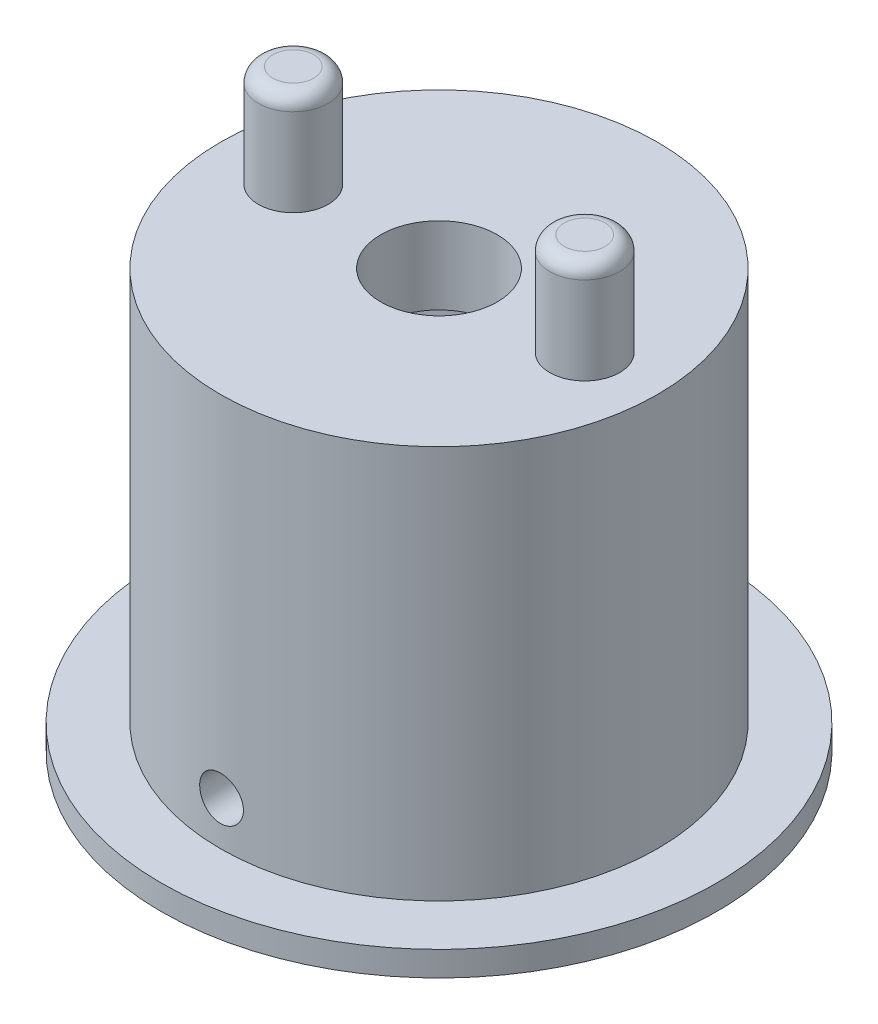
SolidWorks part; units mm, degrees
ref_plane "Front Plane" through (0, 0, 0) normal (0, 0, 1) x (1, 0, 0)
ref_plane "Top Plane" through (0, 0, 0) normal (0, 1, 0) x (1, 0, 0)
ref_plane "Right Plane" through (0, 0, 0) normal (1, 0, 0) x (0, 0, -1)
sketch "Sketch1" plane through (0, 0, 0) normal (0, 1, 0) x (1, 0, 0)
  circle A0 centre (0, 0) radius 15
  dimension "D1" = 30
extrude "Boss-Extrude1" add sketch "Sketch1" along normal blind 27
sketch "Sketch2" plane through (0, 0, 0) normal (0, -1, 0) x (1, 0, 0)
  circle A0 centre (0, 0) radius 19.07
  dimension "D1" = 38.14
extrude "Boss-Extrude2" add sketch "Sketch2" along normal blind 1.7
sketch "Sketch3" plane through (0, -1.7, 0) normal (0, -1, 0) x (1, 0, 0)
  line L1 (0, 5.6003) -> (-4.85, 2.8001)
  line L2 (-4.85, 2.8001) -> (-4.85, -2.8001)
  line L3 (-4.85, -2.8001) -> (0, -5.6003)
  line L4 (0, -5.6003) -> (4.85, -2.8001)
  line L5 (4.85, -2.8001) -> (4.85, 2.8001)
  line L6 (4.85, 2.8001) -> (0, 5.6003)
  circle A0 centre (0, 0) radius 4.85 construction
  dimension "D1" = 9.7
extrude "Cut-Extrude1" cut sketch "Sketch3" against normal blind 23.4
sketch "Sketch4" plane through (0, 21.7, 0) normal (0, -1, 0) x (1, 0, 0)
  circle A0 centre (0, 0) radius 4
  dimension "D1" = 8
extrude "Cut-Extrude2" cut sketch "Sketch4" against normal up to surface (5.3 mm away) up to face at (0, 27, 15)
sketch "Sketch5" plane through (0, 27, 0) normal (0, 1, 0) x (1, 0, 0)
  line L0 (-15, 0) -> (15, 0) construction
  circle A0 centre (0, 0) radius 15 construction
  circle A1 centre (0, 0) radius 15 construction
  circle A2 centre (-10, 0) radius 2.4
  circle A3 centre (10, 0) radius 2.4
  point P11 (-12.4, 0)
  point P12 (12.4, 0)
  dimension "D1" = 4.8
  dimension "D2" = 20
  dimension "D3" = 10
extrude "Boss-Extrude3" add sketch "Sketch5" along normal blind 7
fillet "Fillet1" radius 1 2 edges at (10, 34, 2.4) (-10, 34, 2.4)
sketch "Sketch6" plane through (0, 0, 0) normal (0, 0, 1) x (1, 0, 0)
  line L0 (0, 0) -> (0, 27) construction
  line L1 (15, 27) -> (-15, 27) construction
  circle A0 centre (0, 3) radius 1.5
  dimension "D1" = 3
  dimension "D2" = 24
extrude "Cut-Extrude3" cut sketch "Sketch6" against normal through all and the other way through all
